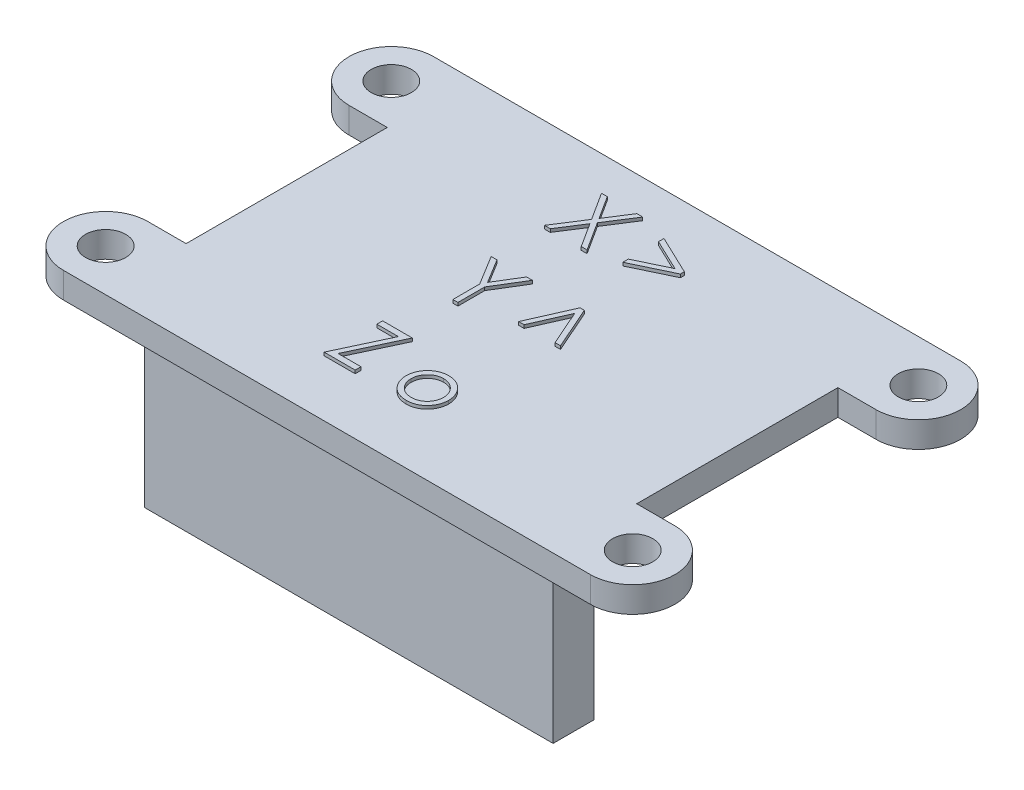
SolidWorks part; units mm, degrees
ref_plane "Front Plane" through (0, 0, 0) normal (0, 0, 1) x (1, 0, 0)
ref_plane "Top Plane" through (0, 0, 0) normal (0, 1, 0) x (1, 0, 0)
ref_plane "Right Plane" through (0, 0, 0) normal (1, 0, 0) x (0, 0, -1)
sketch "Sketch1" plane through (0, 0, 0) normal (0, 1, 0) x (1, 0, 0)
  line L0 (-14, 11.5) -> (-16.375, 11.5)
  line L1 (-14, -11.5) -> (14, -11.5)
  line L2 (-14, -11.5) -> (-14, 11.5) construction
  line L3 (-14, 11.5) -> (14, 11.5)
  line L4 (14, -11.5) -> (14, 11.5) construction
  line L5 (-14, -11.5) -> (14, 11.5) construction
  line L6 (-14, 11.5) -> (14, -11.5) construction
  line L7 (-14, -11.5) -> (-16.375, -11.5)
  line L8 (14, -11.5) -> (16.375, -11.5)
  line L9 (14, 11.5) -> (16.375, 11.5)
  line L10 (14, 6.25) -> (16.375, 6.25)
  line L11 (14, -6.25) -> (16.375, -6.25)
  line L12 (-14, -6.25) -> (-16.375, -6.25)
  line L13 (-14, 6.25) -> (-16.375, 6.25)
  line L14 (-19, 8.875) -> (19, 8.875) construction
  line L15 (-14, 6.25) -> (-14, -6.25)
  line L16 (14, 6.25) -> (14, -6.25)
  arc A0 (-16.375, 6.25) -> (-16.375, 11.5) centre (-16.375, 8.875) cw
  arc A1 (-16.375, -6.25) -> (-16.375, -11.5) centre (-16.375, -8.875) ccw
  arc A2 (16.375, -6.25) -> (16.375, -11.5) centre (16.375, -8.875) cw
  arc A3 (16.375, 6.25) -> (16.375, 11.5) centre (16.375, 8.875) ccw
  point P0 (0, 0)
  dimension "D1" = 23
  dimension "D2" = 28
  dimension "D3" = 5.25
  dimension "D4" = 38
extrude "Boss-Extrude1" add sketch "Sketch1" along normal blind 1.6
sketch "Sketch2" plane through (0, 1.6, 0) normal (0, 1, 0) x (1, 0, 0)
  circle A0 centre (-16.375, 8.875) radius 1.25
  circle A1 centre (16.375, 8.875) radius 1.25
  circle A2 centre (16.375, -8.875) radius 1.25
  circle A3 centre (-16.375, -8.875) radius 1.25
  dimension "D1" = 2.5
extrude "Cut-Extrude1" cut sketch "Sketch2" against normal through all
sketch "Sketch3" plane through (0, 0, 0) normal (0, -1, 0) x (1, 0, 0)
  line L0 (0, 11.5) -> (0, -11.5) construction
  line L1 (-16.375, 11.5) -> (16.375, 11.5) construction
  line L2 (16.375, -11.5) -> (-16.375, -11.5) construction
  line L3 (-16.375, 8.875) -> (16.375, 8.875) construction
  line L4 (-12.7, 7.605) -> (12.7, 7.605)
  line L5 (-12.7, 7.605) -> (-12.7, 10.145)
  line L6 (-12.7, 10.145) -> (12.7, 10.145)
  line L7 (12.7, 7.605) -> (12.7, 10.145)
  line L8 (-12.7, 7.605) -> (12.7, 10.145) construction
  line L9 (-12.7, 10.145) -> (12.7, 7.605) construction
  point P6 (0, 8.875)
  point P15 (0, 0)
  dimension "D1" = 2.54
  dimension "D2" = 25.4
extrude "Boss-Extrude2" add sketch "Sketch3" along normal blind 10
sketch "Sketch4" plane through (0, 1.6, 0) normal (0, 1, 0) x (1, 0, 0)
  text T0 "X >\r\nY ^\r\nZ o"
  point P1 (-3.6052, 3.6338)
  point P2 (-3.8055, 5.6653)
extrude "Boss-Extrude3" add sketch "Sketch4" along normal blind 0.2
